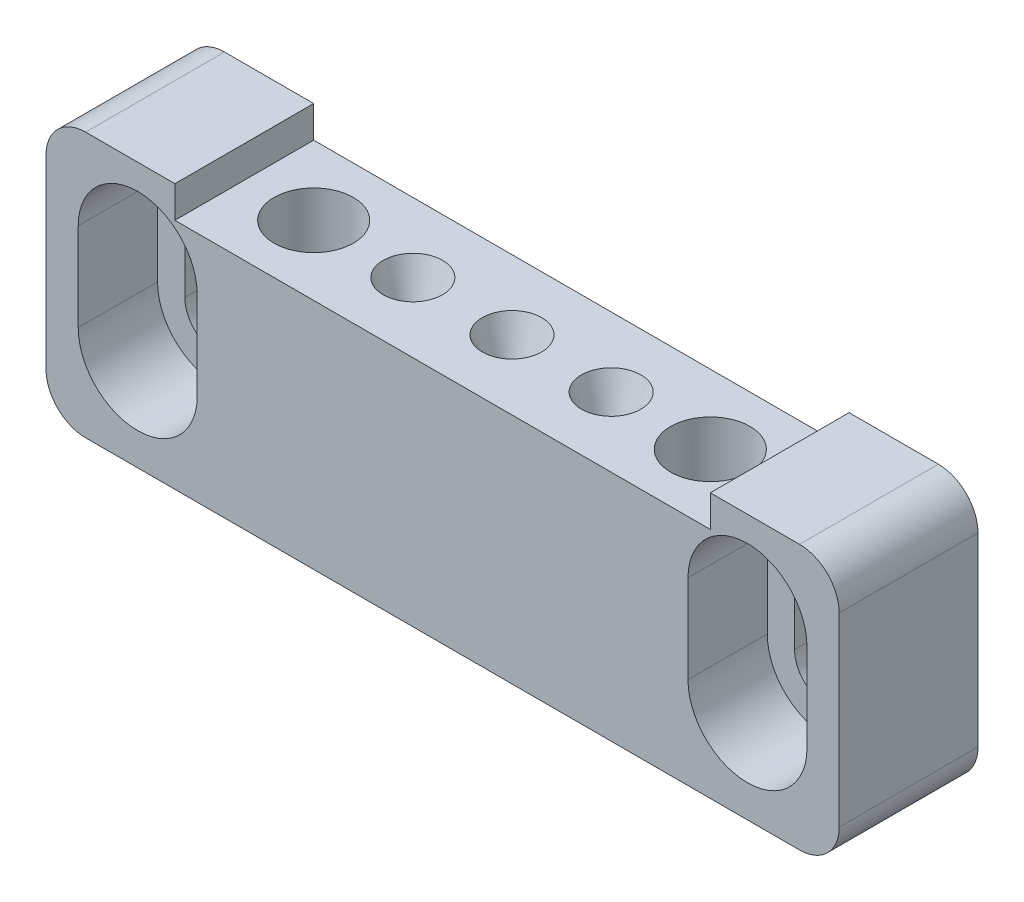
SolidWorks part; units mm, degrees
ref_plane "Front Plane" through (0, 0, 0) normal (0, 0, 1) x (1, 0, 0)
ref_plane "Top Plane" through (0, 0, 0) normal (0, 1, 0) x (1, 0, 0)
ref_plane "Right Plane" through (0, 0, 0) normal (1, 0, 0) x (0, 0, -1)
sketch "Sketch1" plane through (0, 0, 0) normal (0, 0, 1) x (1, 0, 0)
  line L0 (0, 0) -> (18, 0)
  line L1 (20, 2) -> (20, 11.9458)
  line L2 (19.1303, 13.5958) -> (10.5109, 19.5)
  line L3 (9.3807, 19.85) -> (-9.3807, 19.85)
  line L4 (-10.5109, 19.5) -> (-19.1303, 13.5958)
  line L5 (-20, 11.9458) -> (-20, 2)
  line L6 (-18, 0) -> (0, 0)
  line L7 (0, 19.85) -> (0, 0) construction
  line L8 (-15.375, 9.075) -> (-15.375, 4.625) construction
  line L9 (-13.75, 9.075) -> (-13.75, 4.625)
  line L10 (-17, 9.075) -> (-17, 4.625)
  line L11 (15.375, 9.075) -> (15.375, 4.625) construction
  line L12 (17, 9.075) -> (17, 4.625)
  line L13 (13.75, 9.075) -> (13.75, 4.625)
  arc A0 (-13.75, 9.075) -> (-17, 9.075) centre (-15.375, 9.075) ccw
  arc A1 (-17, 4.625) -> (-13.75, 4.625) centre (-15.375, 4.625) ccw
  arc A2 (17, 9.075) -> (13.75, 9.075) centre (15.375, 9.075) ccw
  arc A3 (13.75, 4.625) -> (17, 4.625) centre (15.375, 4.625) ccw
  arc A4 (-9.3807, 19.85) -> (-10.5109, 19.5) centre (-9.3807, 17.85) ccw
  arc A5 (9.3807, 19.85) -> (10.5109, 19.5) centre (9.3807, 17.85) cw
  arc A6 (-20, 11.9458) -> (-19.1303, 13.5958) centre (-18, 11.9458) cw
  arc A7 (19.1303, 13.5958) -> (20, 11.9458) centre (18, 11.9458) cw
  arc A8 (20, 2) -> (18, 0) centre (18, 2) cw
  arc A9 (-20, 2) -> (-18, 0) centre (-18, 2) ccw
  point P10 (-15.375, 6.85)
  point P16 (15.375, 6.85)
  point P23 (15.375, 3)
  point P24 (-15.375, 3)
  point P25 (-15.375, 10.7)
  point P28 (-10, 19.85)
  point P31 (10, 19.85)
  point P34 (-20, 13)
  point P37 (20, 13)
  point P40 (20, 0)
  point P43 (-20, 0)
  dimension "D14" = 2
  dimension "D1" = 20
  dimension "D2" = 20
  dimension "D3" = 19.85
  dimension "D4" = 13
  dimension "D5" = 13
  dimension "D6" = 20
  dimension "D7" = 3.25
  dimension "D8" = 3.25
  dimension "D9" = 3
  dimension "D10" = 3
  dimension "D11" = 7.7
  dimension "D12" = 3
  dimension "D13" = 3
extrude "Boss-Extrude1" add sketch "Sketch1" along normal blind 7
sketch "Sketch2" plane through (0, 0, 7) normal (0, 0, 1) x (1, 0, 0)
  line L0 (-15.375, 4.625) -> (-15.375, 9.075) construction
  line L1 (-18.375, 4.625) -> (-18.375, 9.075)
  line L2 (-12.375, 4.625) -> (-12.375, 9.075)
  line L3 (15.375, 4.625) -> (15.375, 9.075) construction
  line L4 (12.375, 4.625) -> (12.375, 9.075)
  line L5 (18.375, 4.625) -> (18.375, 9.075)
  arc A0 (-18.375, 4.625) -> (-12.375, 4.625) centre (-15.375, 4.625) ccw
  arc A1 (-12.375, 9.075) -> (-18.375, 9.075) centre (-15.375, 9.075) ccw
  arc A2 (12.375, 4.625) -> (18.375, 4.625) centre (15.375, 4.625) ccw
  arc A3 (18.375, 9.075) -> (12.375, 9.075) centre (15.375, 9.075) ccw
  point P4 (-15.375, 6.85)
  point P9 (15.375, 6.85)
  dimension "D1" = 6
  dimension "D2" = 6
extrude "Cut-Extrude1" cut sketch "Sketch2" against normal blind 4
sketch "Sketch6" plane through (0, 0, 7) normal (0, 0, 1) x (1, 0, 0)
  line L0 (-20, 11.9458) -> (-20, 2) construction
  line L1 (-13.5, 13.35) -> (-6.5, 13.35)
  line L2 (-13.5, 13.35) -> (-13.5, 11.75)
  line L3 (-13.5, 11.75) -> (13.5, 11.75)
  line L4 (13.5, 13.35) -> (13.5, 11.75)
  line L5 (-13.5, 13.35) -> (13.5, 11.75) construction
  line L6 (-13.5, 11.75) -> (13.5, 13.35) construction
  line L7 (20, 2) -> (20, 11.9458) construction
  line L8 (-18, 0) -> (18, 0) construction
  line L9 (-6.5, 13.35) -> (-6.5, 19.85)
  line L11 (-6.5, 19.85) -> (6.5, 19.85)
  line L12 (6.5, 19.85) -> (6.5, 13.35)
  line L14 (6.5, 13.35) -> (13.5, 13.35)
  line L15 (9.3807, 19.85) -> (-9.3807, 19.85) construction
  point P4 (0, 12.55)
  point P6 (0, 0)
  point P20 (0, 0)
  point P21 (0, 0)
  point P22 (0, 0)
  point P23 (0, 0)
  dimension "D1" = 6.5
  dimension "D2" = 6.5
  dimension "D3" = 11.75
  dimension "D4" = 1.6
  dimension "D5" = 7
  dimension "D6" = 7
  dimension "D7" = 13
  dimension "D8" = 6.5
  dimension "D9" = 0
extrude "Cut-Extrude4" cut sketch "Sketch6" against normal through all
sketch "Sketch8" plane through (0, 19.85, 0) normal (0, 1, 0) x (1, 0, 0)
  line L0 (-6.5, 0) -> (-9.3807, 0) construction
  line L1 (9.3807, 0) -> (6.5, 0) construction
  circle A0 centre (-10, -3.5) radius 2
  circle A1 centre (10, -3.5) radius 2
  dimension "D1" = 4
  dimension "D2" = 10
  dimension "D4" = 3.5
  dimension "D5" = 3.5
  dimension "D3" = 10
extrude "Cut-Extrude5" cut sketch "Sketch8" against normal blind 18
sketch "Sketch9" plane through (0, 19.85, 0) normal (0, 1, 0) x (1, 0, 0)
  circle A0 centre (10, -3.5) radius 3
  circle A1 centre (-10, -3.5) radius 3
  dimension "D1" = 6
extrude "Cut-Extrude6" cut sketch "Sketch9" against normal up to surface (8.1 mm away) up to face at (-10, 11.75, 1.5)
sketch "Sketch10" plane through (0, 0, 7) normal (0, 0, 1) x (1, 0, 0)
  line L0 (-6.5, 13.35) -> (-13.5, 13.35) construction
  line L1 (-20, 19.85) -> (20, 19.85)
  line L2 (-20, 19.85) -> (-20, 13.35)
  line L3 (-20, 13.35) -> (20, 13.35)
  line L4 (20, 19.85) -> (20, 13.35)
  line L5 (-20, 19.85) -> (20, 13.35) construction
  line L6 (-20, 13.35) -> (20, 19.85) construction
  line L7 (-20, 11.9458) -> (-20, 2) construction
  line L8 (20, 2) -> (20, 11.9458) construction
  line L9 (9.3807, 19.85) -> (6.5, 19.85) construction
  point P4 (0, 16.6)
extrude "Cut-Extrude7" cut sketch "Sketch10" against normal through all
fillet "Fillet1" radius 2 2 edges at (-19.4241, 13.35, 3.5) (19.4241, 13.35, 3.5)
sketch "Sketch11" plane through (0, 11.75, 0) normal (0, 1, 0) x (1, 0, 0)
  line L0 (-10, -3.5) -> (10, -3.5) construction
  line L1 (0, 0) -> (0, -6.3575) construction
  circle A0 centre (0, -3.5) radius 1.5
  circle A1 centre (5, -3.5) radius 1.5
  circle A2 centre (-5, -3.5) radius 1.5
  point P12 (0, -3.9895)
  point P14 (0, 0)
  point P15 (-5, -3.5)
  point P16 (5, -3.5)
  dimension "D1" = 3
  dimension "D2" = 5
  dimension "D3" = 5
extrude "Cut-Extrude8" cut sketch "Sketch11" against normal blind 3 draft 20
